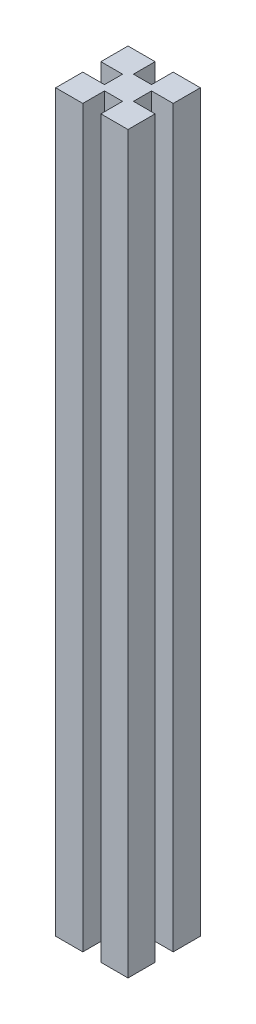
SolidWorks part; units mm, degrees
ref_plane "Front Plane" through (0, 0, 0) normal (0, 0, 1) x (1, 0, 0)
ref_plane "Top Plane" through (0, 0, 0) normal (0, 1, 0) x (1, 0, 0)
ref_plane "Right Plane" through (0, 0, 0) normal (1, 0, 0) x (0, 0, -1)
sketch "Sketch1" plane through (0, 0, 0) normal (0, 1, 0) x (1, 0, 0)
  line L1 (-10, -10) -> (10, -10)
  line L2 (-10, -10) -> (-10, 10)
  line L3 (-10, 10) -> (10, 10)
  line L4 (10, -10) -> (10, 10)
  line L5 (-10, -10) -> (10, 10) construction
  line L6 (-10, 10) -> (10, -10) construction
  point P0 (0, 0)
  dimension "D1" = 20
  dimension "D2" = 20
extrude "Boss-Extrude1" add sketch "Sketch1" along normal blind 101.6 and the other way blind 101.6
sketch "Sketch2" plane through (0, 0, 0) normal (0, 1, 0) x (1, 0, 0)
  line L0 (-2.5, 4) -> (2.5, 4)
  line L1 (-2.5, 4) -> (-2.5, 16)
  line L2 (-2.5, 16) -> (2.5, 16)
  line L3 (2.5, 4) -> (2.5, 16)
  line L4 (-2.5, 4) -> (2.5, 16) construction
  line L5 (-2.5, 16) -> (2.5, 4) construction
  line L6 (4, 2.5) -> (16, 2.5)
  line L7 (4, 2.5) -> (4, -2.5)
  line L8 (4, -2.5) -> (16, -2.5)
  line L9 (16, 2.5) -> (16, -2.5)
  line L10 (4, 2.5) -> (16, -2.5) construction
  line L11 (4, -2.5) -> (16, 2.5) construction
  line L12 (-10, 10) -> (10, -10) construction
  line L13 (-16, 2.5) -> (-4, -2.5) construction
  line L14 (-4, 2.5) -> (-16, -2.5) construction
  line L15 (-4, -2.5) -> (-16, -2.5)
  line L16 (-16, 2.5) -> (-16, -2.5)
  line L17 (-4, 2.5) -> (-16, 2.5)
  line L18 (-4, 2.5) -> (-4, -2.5)
  line L19 (2.5, -4) -> (2.5, -16)
  line L20 (2.5, -4) -> (-2.5, -16) construction
  line L21 (-2.5, -4) -> (2.5, -16) construction
  line L22 (-2.5, -16) -> (2.5, -16)
  line L23 (-2.5, -4) -> (2.5, -4)
  line L24 (-2.5, -4) -> (-2.5, -16)
  line L25 (-10, 10) -> (-10, -10) construction
  line L26 (10, -10) -> (10, 10) construction
  line L27 (-10, -10) -> (10, -10) construction
  line L28 (10, 10) -> (-10, 10) construction
  point P0 (0, 10)
  point P5 (10, 0)
  point P16 (-10, 0)
  point P21 (0, -10)
  dimension "D1" = 5
  dimension "D2" = 12
  dimension "D3" = 5
  dimension "D4" = 12
extrude "Cut-Extrude1" cut sketch "Sketch2" against normal through all both and the other way through all
